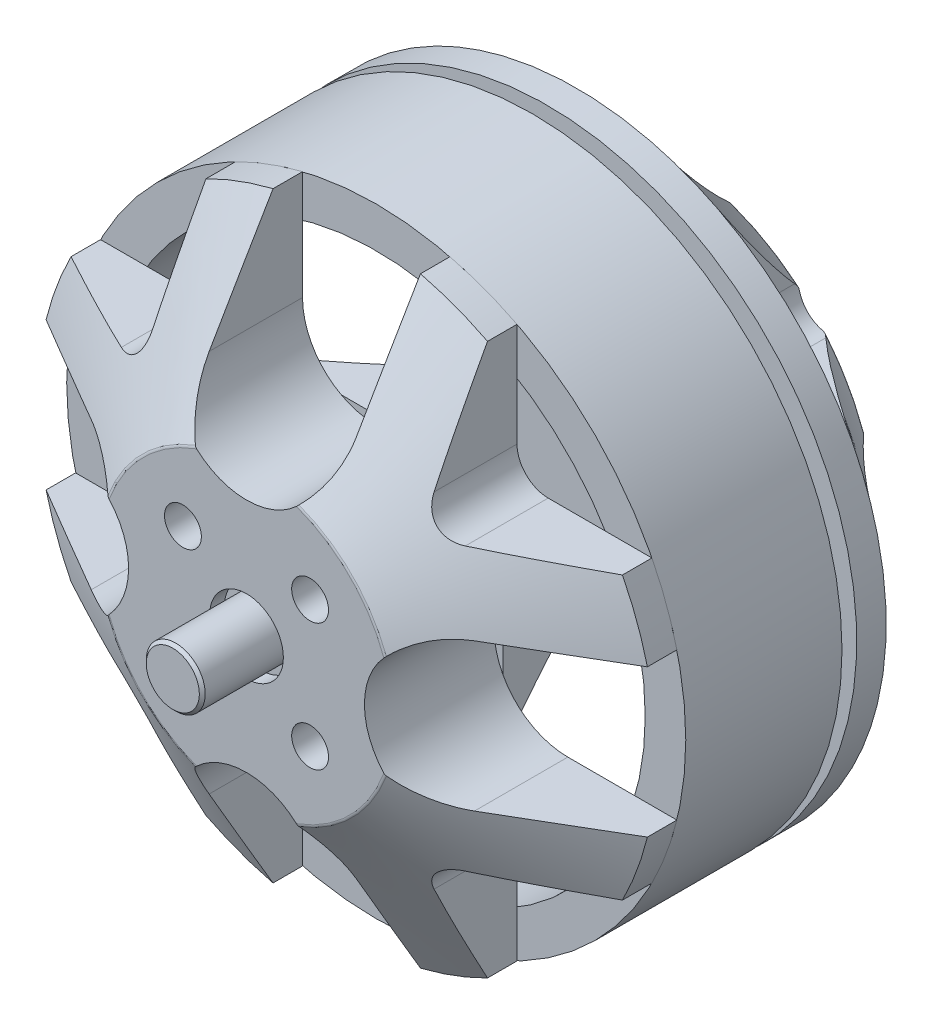
SolidWorks part; units mm, degrees
ref_plane "前视基准面" through (0, 0, 0) normal (0, 0, 1) x (1, 0, 0)
ref_plane "上视基准面" through (0, 0, 0) normal (0, 1, 0) x (1, 0, 0)
ref_plane "右视基准面" through (0, 0, 0) normal (1, 0, 0) x (0, 0, -1)
sketch "草图1" plane through (0, 0, 0) normal (0, 0, 1) x (1, 0, 0)
  circle A0 centre (0, 0) radius 21
  dimension "D1" = 42
extrude "凸台-拉伸1" add sketch "草图1" along normal blind 10.6
sketch "草图2" plane through (0, 0, 10.6) normal (0, 0, 1) x (1, 0, 0)
  circle A1 centre (0, 0) radius 21
  circle A2 centre (0, 0) radius 21
  dimension "D1" = 0
extrude "凸台-拉伸2" add sketch "草图2" along normal blind 2 separate body
ref_plane "基准面1" through (0, 0, 19.4) normal (0, 0, 1) x (1, 0, 0)
sketch "草图3" plane through (0, 0, 19.4) normal (0, 0, 1) x (1, 0, 0)
  circle A0 centre (0, 0) radius 10
  dimension "D1" = 20
sketch "草图4" plane through (0, 0, 12.6) normal (0, 0, 1) x (1, 0, 0)
  circle A1 centre (0, 0) radius 21
  circle A2 centre (0, 0) radius 21
  dimension "D1" = 0
loft "放样1" add profiles "草图4", "草图3" connector at (-16.9115, -12.45, 12.6) connector at (-6.8363, -7.2983, 19.4)
sketch "草图5" plane through (0, 0, 19.4) normal (0, 0, 1) x (1, 0, 0)
  line L0 (0, 21) -> (22.208, 21) construction
  line L1 (-5, 13) -> (-5, 24.1933)
  line L2 (-5, 24.1933) -> (5, 24.1933)
  line L3 (5, 24.1933) -> (5, 13)
  arc A0 (-5, 13) -> (5, 13) centre (0, 13) ccw
  circle A1 centre (0, 0) radius 21 construction
  dimension "D2" = 10
  dimension "D1" = 8
sketch "草图6" plane through (0, 0, 10.6) normal (0, 0, -1) x (-1, 0, 0)
  line L0 (5, 24.1933) -> (-5, 24.1933) construction
  line L1 (5, 13) -> (5, 24.1933) construction
  line L2 (-5, 24.1933) -> (-5, 13) construction
  line L3 (5, 24.1933) -> (-5, 24.1933)
  line L4 (5, 13) -> (5, 24.1933)
  line L5 (-5, 24.1933) -> (-5, 13)
  arc A0 (-5, 13) -> (5, 13) centre (0, 13) ccw construction
  arc A1 (-5, 13) -> (5, 13) centre (0, 13) ccw
extrude "切除-拉伸1" cut sketch "草图6" against normal blind 11
pattern_circular "阵列(圆周)1" count 4 every 90 about axis through (0, 0, 12.6) along (0, 0, -1) of "切除-拉伸1"
sketch "草图7" plane through (0, 0, 19.4) normal (0, 0, 1) x (1, 0, 0)
  line L0 (0, 0) -> (0, 6.168) construction
  line L1 (0, 0) -> (5.6424, 0) construction
  line L2 (0, 0) -> (10.1705, 10.1705) construction
  line L4 (9.5506, 11.6673) -> (9.5506, 19.6594)
  line L5 (9.5506, 19.6594) -> (19.9844, 19.6594)
  line L6 (19.9844, 19.6594) -> (19.9844, 9.5506)
  line L7 (19.9844, 9.5506) -> (11.6673, 9.5506)
  arc A0 (9.5506, 11.6673) -> (11.6673, 9.5506) centre (11.6673, 11.6673) ccw
  dimension "D1" = 45
extrude "切除-拉伸2" cut sketch "草图7" against normal blind 21
pattern_circular "阵列(圆周)2" count 4 every 90 about axis through (0, 0, 12.6) along (0, 0, -1) of "切除-拉伸2" reverse direction yes
sketch "草图8" plane through (0, 0, 19.4) normal (0, 0, 1) x (1, 0, 0)
  line L0 (0, 0) -> (12.5019, 0) construction
  line L1 (0, 0) -> (0, 10.6487) construction
  line L2 (0, 0) -> (-24.3745, -24.3745) construction
  line L3 (0, 0) -> (17.1017, 17.1017) construction
  line L4 (0, 0) -> (-8.3899, 8.3899) construction
  line L5 (0, 0) -> (9.1866, -9.1866) construction
  circle A0 centre (0, 0) radius 6.1 construction
  circle A1 centre (-4.3134, 4.3134) radius 1.25
  circle A2 centre (4.3134, 4.3134) radius 1.25
  circle A3 centre (-4.3134, -4.3134) radius 1.25
  circle A4 centre (4.3134, -4.3134) radius 1.25
  dimension "D1" = 12.2
  dimension "D6" = 2.5
  dimension "D7" = 2.5
  dimension "D8" = 2.5
  dimension "D9" = 2.5
  dimension "D2" = 45
  dimension "D3" = 135
  dimension "D4" = 45
  dimension "D5" = 45
extrude "切除-拉伸3" cut sketch "草图8" against normal blind 21
sketch "草图9" plane through (0, 0, 19.4) normal (0, 0, 1) x (1, 0, 0)
  circle A0 centre (0, 0) radius 2.5
  dimension "D1" = 5
extrude "切除-拉伸4" cut sketch "草图9" against normal blind 1
sketch "草图10" plane through (0, 0, 18.4) normal (0, 0, 1) x (1, 0, 0)
  circle A2 centre (0, 0) radius 2
  circle A3 centre (0, 0) radius 2
  dimension "D1" = 0.5
extrude "凸台-拉伸3" add sketch "草图10" along normal blind 6
chamfer "倒角1" distance 0.2 angle 45 1 edges at (2, 0, 24.4)
fillet "圆角1" radius 0.3 1 edges
fillet "圆角2" radius 0.3 3 edges
sketch "草图12" plane through (0, 0, 10.6) normal (0, 0, 1) x (1, 0, 0)
  circle A1 centre (0, 0) radius 18.25
  dimension "D1" = 36.5
extrude "切除-拉伸5" cut sketch "草图12" against normal blind 12
ref_plane "基准面2" through (0, 0, -1) normal (0, 0, -1) x (-1, 0, 0)
sketch "草图14" plane through (0, 0, -1) normal (0, 0, -1) x (-1, 0, 0)
  circle A0 centre (0, 0) radius 21
  circle A1 centre (0, 0) radius 19.4
  dimension "D1" = 38.8
extrude "凸台-拉伸4" add sketch "草图14" along normal blind 2 separate body
ref_plane "基准面3" through (0, 0, -8.5) normal (0, 0, -1) x (-1, 0, 0)
sketch "草图15" plane through (0, 0, -8.5) normal (0, 0, -1) x (-1, 0, 0)
  circle A0 centre (0, 0) radius 14.85
  dimension "D1" = 29.7
sketch "草图16" plane through (0, 0, -3) normal (0, 0, -1) x (-1, 0, 0)
  circle A1 centre (0, 0) radius 21
  circle A2 centre (0, 0) radius 21
  dimension "D1" = 0
loft "放样2" add profiles "草图16", "草图15" connector at (20.1214, 6.0107, -3) connector at (11.5602, 9.3212, -8.5)
sketch "草图17" plane through (0, 0, -8.5) normal (0, 0, -1) x (-1, 0, 0)
  line L0 (5, 13) -> (5, 20.3961) construction
  line L1 (-5, 20.3961) -> (-5, 13) construction
  line L2 (5, 13) -> (5, 20.3961)
  line L3 (-5, 20.3961) -> (-5, 13)
  circle A0 centre (0, 0) radius 21 construction
  arc A1 (-5, 13) -> (5, 13) centre (0, 13) ccw construction
  arc A2 (5, 20.3961) -> (-5, 20.3961) centre (0, 0) ccw
  arc A3 (-5, 13) -> (5, 13) centre (0, 13) ccw
extrude "切除-拉伸7" cut sketch "草图17" against normal up to surface (5.5 mm away) up to face at (-19.4, 0, -3)
pattern_circular "阵列(圆周)3" count 4 every 90 about axis through (0, 0, 10.6) along (0, 0, -1) of "切除-拉伸7" reverse direction yes
sketch "草图18" plane through (0, 0, -8.5) normal (0, 0, -1) x (-1, 0, 0)
  line L0 (-18.7026, -9.5506) -> (-11.6673, -9.5506) construction
  line L1 (-9.5506, -11.6673) -> (-9.5506, -18.7026) construction
  line L2 (-18.7026, -9.5506) -> (-11.6673, -9.5506)
  line L3 (-9.5506, -11.6673) -> (-9.5506, -18.7026)
  circle A0 centre (0, 0) radius 21 construction
  arc A1 (-9.5506, -11.6673) -> (-11.6673, -9.5506) centre (-11.6673, -11.6673) ccw construction
  arc A2 (-18.7026, -9.5506) -> (-9.5506, -18.7026) centre (0, 0) ccw
  arc A3 (-9.5506, -11.6673) -> (-11.6673, -9.5506) centre (-11.6673, -11.6673) ccw
extrude "切除-拉伸8" cut sketch "草图18" against normal up to surface (5.5 mm away) up to face at (19.8852, 0, -3)
pattern_circular "阵列(圆周)4" count 4 every 90 about axis through (0, 0, 10.6) along (0, 0, -1) of "切除-拉伸8"
fillet "圆角3" radius 0.3 8 edges
sketch "草图19" plane through (0, 0, -8.5) normal (0, 0, -1) x (-1, 0, 0)
  circle A0 centre (0, 0) radius 5.75
  dimension "D1" = 11.5
extrude "切除-拉伸10" cut sketch "草图19" against normal blind 1
sketch "草图20" plane through (0, 0, -7.5) normal (0, 0, -1) x (-1, 0, 0)
  circle A0 centre (0, 0) radius 3
  dimension "D1" = 6
extrude "凸台-拉伸5" add sketch "草图20" along normal blind 5
sketch "草图21" plane through (0, 0, -12.5) normal (0, 0, -1) x (-1, 0, 0)
  circle A1 centre (0, 0) radius 3
  circle A2 centre (0, 0) radius 3
  dimension "D1" = 0
extrude "切除-拉伸11" cut sketch "草图21" against normal blind 2
chamfer "倒角4" distance 1 angle 45 1 edges at (-3, 0, -10.5)
